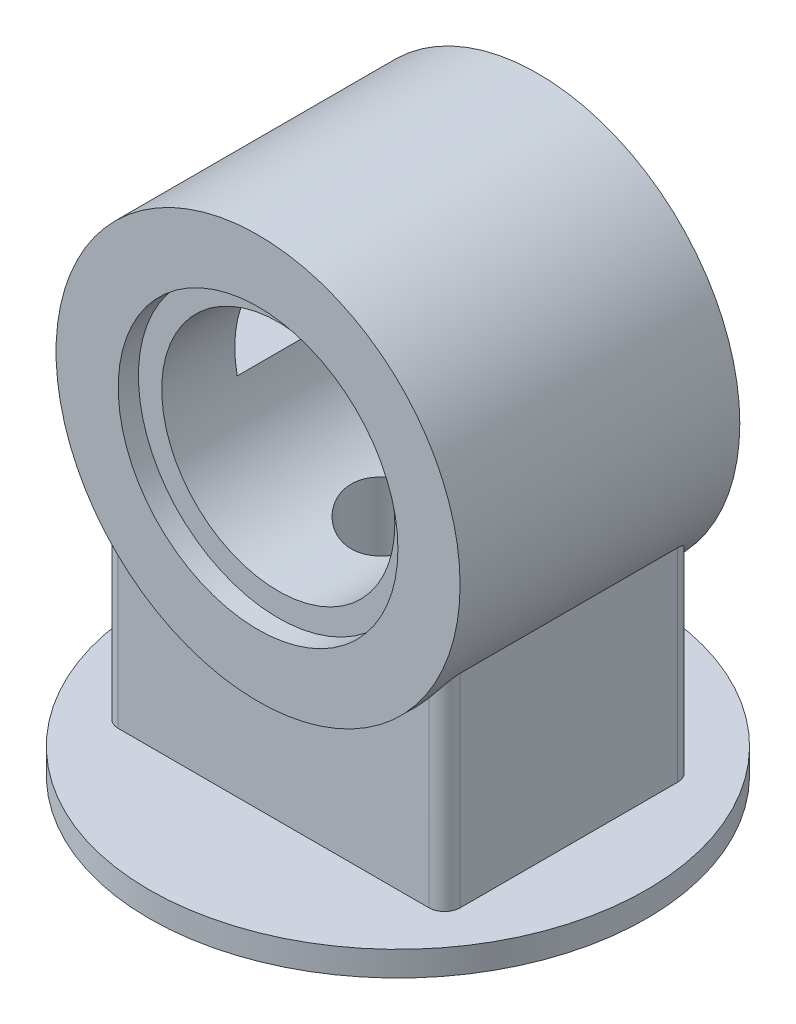
SolidWorks part; units mm, degrees
ref_plane "前视基准面" through (0, 0, 0) normal (0, 0, 1) x (1, 0, 0)
ref_plane "上视基准面" through (0, 0, 0) normal (0, 1, 0) x (1, 0, 0)
ref_plane "右视基准面" through (0, 0, 0) normal (1, 0, 0) x (0, 0, -1)
other "Configuration Table"
sketch "草图1" plane through (0, 0, 0) normal (0, 1, 0) x (1, 0, 0)
  circle A0 centre (0, 0) radius 35
  circle A1 centre (0, 0) radius 17.25 construction
  circle A2 centre (0, 17.25) radius 2
  circle A3 centre (14.9389, 8.625) radius 2
  circle A4 centre (14.9389, -8.625) radius 2
  circle A5 centre (0, -17.25) radius 2
  circle A6 centre (-14.9389, -8.625) radius 2
  circle A7 centre (-14.9389, 8.625) radius 2
  point P19 (0, 0)
  dimension "D1" = 70
  dimension "D2" = 6
extrude "凸台-拉伸1" add sketch "草图1" along normal blind 7
sketch "草图2" plane through (0, 7, 0) normal (0, 1, 0) x (1, 0, 0)
  circle A0 centre (0, 0) radius 160
  dimension "D1" = 320
extrude "凸台-拉伸2" add sketch "草图2" along normal blind 16 contours A0
sketch "草图3" plane through (0, 0, 0) normal (0, 0, 1) x (1, 0, 0)
  line L0 (160, 23) -> (-160, 23) construction
  circle A0 centre (0, 223) radius 130
  circle A1 centre (0, 223) radius 75
  dimension "D1" = 150
  dimension "D2" = 260
  dimension "D3" = 200
extrude "凸台-拉伸4" add sketch "草图3" along normal mid plane 180 separate body
sketch "草图4" plane through (0, 23, 0) normal (0, 1, 0) x (1, 0, 0)
  line L1 (-110, 80) -> (110, 80)
  line L2 (-110, 80) -> (-110, -80)
  line L3 (-110, -80) -> (110, -80)
  line L4 (110, 80) -> (110, -80)
  line L5 (0, -80) -> (0, 80) construction
  line L6 (-110, 0) -> (110, 0) construction
  point P0 (0, 0)
  dimension "D1" = 160
  dimension "D2" = 220
extrude "凸台-拉伸5" add sketch "草图4" along normal up to next
fillet "圆角1" radius 10 4 edges at (-110, 88.359, -80) (110, 88.359, -80) (110, 88.359, 80) (-110, 88.359, 80)
sketch "草图5" plane through (0, 0, 0) normal (0, -1, 0) x (1, 0, 0)
  circle A0 centre (0, 0) radius 30
extrude "切除-拉伸1" cut sketch "草图5" against normal blind 220 from offset 30 offset against normal yes
sketch "草图6" plane through (0, 0, 0) normal (0, -1, 0) x (1, 0, 0)
  circle A0 centre (0, 0) radius 17.25 construction
  circle A1 centre (0, 17.25) radius 2
  circle A2 centre (14.9389, 8.625) radius 2
  circle A3 centre (14.9389, -8.625) radius 2
  circle A4 centre (0, -17.25) radius 2
  circle A5 centre (-14.9389, -8.625) radius 2
  circle A6 centre (-14.9389, 8.625) radius 2
  point P18 (0, 0)
  dimension "D1" = 6
extrude "切除-拉伸2" cut sketch "草图6" against normal blind 220
sketch "草图7" plane through (0, 7, 0) normal (0, -1, 0) x (1, 0, 0)
  circle A0 centre (0, 0) radius 80
extrude "拉伸-薄壁1" add sketch "草图7" along normal blind 2 thin thin type one direction reverse wall 52
sketch "草图8" plane through (0, 0, 90) normal (0, 0, 1) x (1, 0, 0)
  circle A0 centre (0, 223) radius 90
  dimension "D1" = 180
extrude "切除-拉伸3" cut sketch "草图8" against normal blind 13
sketch "草图9" plane through (0, 0, -90) normal (0, 0, -1) x (-1, 0, 0)
  circle A0 centre (0, 223) radius 100 construction
  circle A1 centre (0, 323) radius 5
  circle A2 centre (50, 309.6025) radius 5
  circle A3 centre (86.6025, 273) radius 5
  circle A4 centre (100, 223) radius 5
  circle A5 centre (86.6025, 173) radius 5
  circle A6 centre (50, 136.3975) radius 5
  circle A7 centre (0, 123) radius 5
  circle A8 centre (-50, 136.3975) radius 5
  circle A9 centre (-86.6025, 173) radius 5
  circle A10 centre (-100, 223) radius 5
  circle A11 centre (-86.6025, 273) radius 5
  circle A12 centre (-50, 309.6025) radius 5
  point P30 (0, 223)
  dimension "D1" = 200
  dimension "D2" = 10
  dimension "D3" = 12
extrude "切除-拉伸4" cut sketch "草图9" against normal blind 30
sketch "草图10" plane through (0, 0, 0) normal (1, 0, 0) x (0, 0, -1)
  line L0 (0, 353) -> (0, 123.9542) construction
  line L1 (90, 353) -> (-90, 353) construction
  line L3 (-30, 267.738) -> (30, 267.738)
  line L4 (-30, 267.738) -> (-30, 207.738)
  line L5 (-30, 207.738) -> (30, 207.738)
  line L6 (30, 267.738) -> (30, 207.738)
  line L7 (0, 207.738) -> (0, 267.738) construction
  line L8 (-30, 237.738) -> (30, 237.738) construction
  point P5 (0, 237.738)
  point P9 (0, 246.8451)
  point P10 (0, 237.738)
  dimension "D1" = 60
extrude "切除-拉伸5" cut sketch "草图10" against normal blind 170
